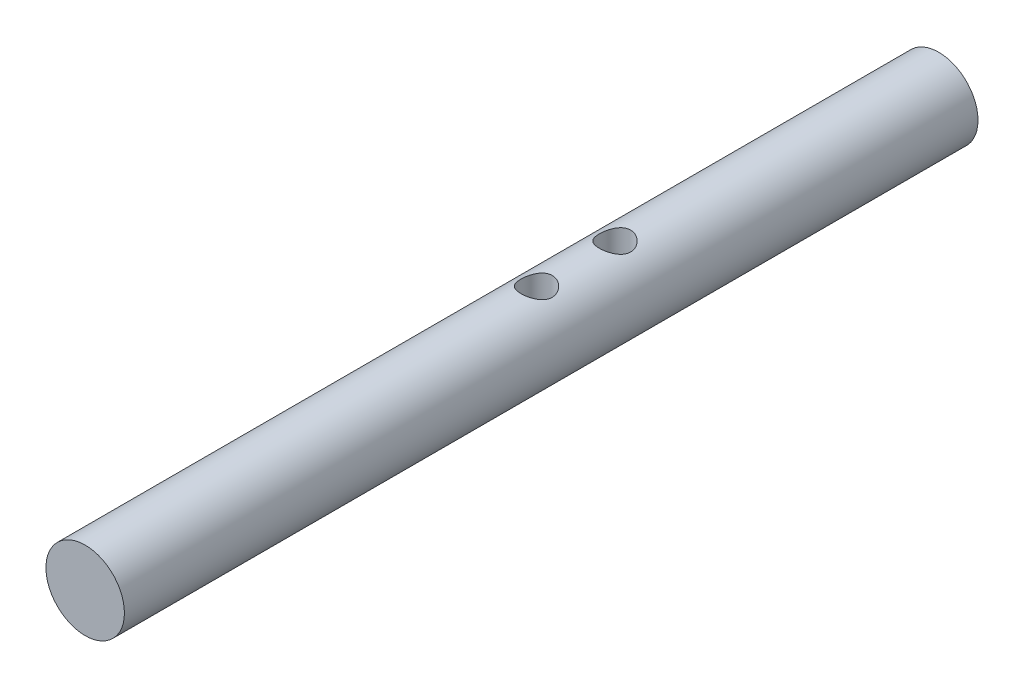
SolidWorks part; units mm, degrees
material "6061 合金"
ref_plane "正面" through (0, 0, 0) normal (0, 0, 1) x (1, 0, 0)
ref_plane "平面" through (0, 0, 0) normal (0, 1, 0) x (1, 0, 0)
ref_plane "右側面" through (0, 0, 0) normal (1, 0, 0) x (0, 0, -1)
sketch "断面" plane through (0, 0, 0) normal (0, 0, 1) x (1, 0, 0)
  circle A0 centre (0, 0) radius 4
  dimension "D1" = 8
extrude "軸全長" add sketch "断面" along normal blind 87
ref_axis "中心軸" through (0, 0, 87) along (0, 0, -1)
ref_plane "上面" through (0, 4, 0) normal (0, 1, 0) x (1, 0, 0)
sketch "上面穴スケッチ" plane through (0, 4, 0) normal (0, 1, 0) x (1, 0, 0)
  line L0 (0, -87) -> (0, 0) construction
  line L1 (4, 0) -> (-4, 0) construction
  circle A0 centre (0, -33) radius 1.6
  circle A1 centre (0, -41) radius 1.6
  dimension "D1" = 33
  dimension "D2" = 3.2
  dimension "D3" = 8
extrude "上面穴貫通" cut sketch "上面穴スケッチ" against normal through all
sketch "上面キー溝スケッチ" plane through (0, 4, 0) normal (0, 1, 0) x (1, 0, 0)
  line L0 (0, -30) -> (0, -50) construction
  line L1 (0, -87) -> (0, 0) construction
  line L2 (1.5, -30) -> (1.5, -50)
  line L3 (-1.5, -30) -> (-1.5, -50)
  line L4 (4, 0) -> (-4, 0) construction
  arc A0 (1.5, -30) -> (-1.5, -30) centre (0, -30) ccw
  arc A1 (-1.5, -50) -> (1.5, -50) centre (0, -50) ccw
  point P5 (0, -40)
  dimension "D1" = 3
  dimension "D2" = 30
  dimension "D3" = 20
extrude "上面キー溝1.6mm" [suppressed] cut sketch "上面キー溝スケッチ" against normal blind 1.6
sketch "上面Dカットスケッチ" plane through (0, 4, 0) normal (0, 1, 0) x (1, 0, 0)
  line L0 (-4, 0) -> (-4, -87) construction
  line L1 (4, -87) -> (-4, -87)
  line L2 (4, -87) -> (4, -77)
  line L3 (4, -77) -> (-4, -77)
  line L4 (-4, -87) -> (-4, -77)
  dimension "D1" = 10
extrude "上面Dカット1mm" [suppressed] cut sketch "上面Dカットスケッチ" against normal blind 1
sketch "Eリング溝スケッチ" plane through (0, 0, 0) normal (0, 1, 0) x (1, 0, 0)
  line L0 (4, -87) -> (4, 0) construction
  line L1 (4, -1) -> (3, -1)
  line L2 (4, -1) -> (4, -2)
  line L3 (4, -2) -> (3, -2)
  line L4 (3, -1) -> (3, -2)
  line L5 (4, 0) -> (-4, 0) construction
  dimension "D1" = 1
  dimension "D2" = 1
revolve "Eリング溝カット" [suppressed] cut sketch "Eリング溝スケッチ" angle 360 about axis through (0, 0, 87) along (0, 0, -1)
